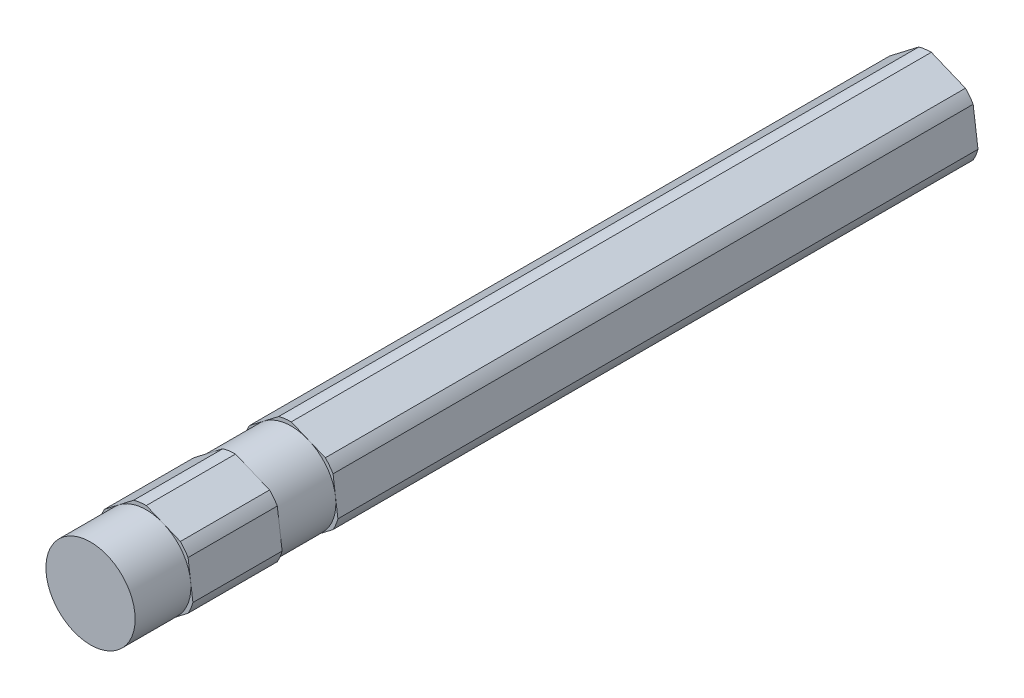
SolidWorks part; units mm, degrees
material "6061-T6 (SS)"
ref_plane "Front Plane" through (0, 0, 0) normal (0, 0, 1) x (1, 0, 0)
ref_plane "Top Plane" through (0, 0, 0) normal (0, 1, 0) x (1, 0, 0)
ref_plane "Right Plane" through (0, 0, 0) normal (1, 0, 0) x (0, 0, -1)
sketch "Sketch1" plane through (0, 0, 0) normal (0, 0, 1) x (1, 0, 0)
  line L1 (-1.7899, 6.6335) -> (-5.9502, 3.4354)
  line L2 (-6.6397, 1.7666) -> (-5.9502, -3.4353)
  line L3 (-4.8498, -4.8668) -> (0, -6.8707)
  line L4 (1.7899, -6.6335) -> (5.9502, -3.4354)
  line L5 (6.6397, -1.7666) -> (5.9502, 3.4353)
  line L6 (4.8498, 4.8668) -> (0, 6.8707)
  circle A0 centre (0, 0) radius 6.35 construction
  arc A1 (-5.9502, 3.4354) -> (-6.6397, 1.7666) centre (0, 0) ccw
  arc A2 (-5.9502, -3.4353) -> (-4.8498, -4.8668) centre (0, 0) ccw
  arc A3 (0, -6.8707) -> (1.7899, -6.6335) centre (0, 0) ccw
  arc A4 (5.9502, -3.4354) -> (6.6397, -1.7666) centre (0, 0) ccw
  arc A5 (5.9502, 3.4353) -> (4.8498, 4.8668) centre (0, 0) ccw
  arc A6 (0, 6.8707) -> (-1.7899, 6.6335) centre (0, 0) ccw
  dimension "D1" = 12.7
  dimension "D2" = 13.7414
extrude "Boss-Extrude1" add sketch "Sketch1" along normal blind 119.6975 contours L1 A1 L2 A2 L3 A3 L4 A4 L5 A5 L6 A6
sketch "Sketch8" plane through (0, 0, 0) normal (0, 0, -1) x (-1, 0, 0)
  point P0 (0, 0)
hole_wizard "1/4-20 Tapped Hole2" positions "Sketch11" profile "Sketch12" tap size "1/4-20" standard "ANSI Inch"
sketch "Sketch11" plane through (0, 0, 0) normal (0, 0, -1) x (-1, 0, 0)
  point P0 (0, 0)
cosmetic thread "Hole Thread5" parameters "D1"=12.7, "D2"=6.35
sketch "Sketch12" plane through (0, 0, 0) normal (1, 0, 0) x (0, 1, 0)
  line L0 (0, 0) -> (0, 18.0438)
  line L1 (0, 18.0438) -> (2.5527, 16.51)
  line L2 (2.5527, 16.51) -> (2.5527, 0)
  line L5 (2.5527, 0) -> (0, 0)
  line L10 (0, 18.0438) -> (-2.5527, 16.51) construction
  line L11 (0, -6.35) -> (0, 107.95) construction
  dimension "Tap Drill Dia." = 5.1054
  dimension "Tap Drill Depth" = 16.51
  dimension "Drill Angle" = 118
sketch "Sketch14" plane through (0, 0, 119.6975) normal (0, 0, 1) x (1, 0, 0)
  line L0 (4.8498, 4.8668) -> (0, 6.8707) construction
  line L7 (-1.7899, 6.6335) -> (-5.9502, 3.4354)
  line L8 (-6.6397, 1.7666) -> (-5.9502, -3.4353)
  line L9 (-4.8498, -4.8668) -> (0, -6.8707)
  line L10 (1.7899, -6.6335) -> (5.9502, -3.4354)
  line L11 (6.6397, -1.7666) -> (5.9502, 3.4353)
  line L12 (4.8498, 4.8668) -> (0, 6.8707)
  line L13 (-1.7899, 6.6335) -> (-5.9502, 3.4354)
  line L14 (-6.6397, 1.7666) -> (-5.9502, -3.4353)
  line L15 (-4.8498, -4.8668) -> (0, -6.8707)
  line L16 (1.7899, -6.6335) -> (5.9502, -3.4354)
  line L17 (6.6397, -1.7666) -> (5.9502, 3.4353)
  line L18 (4.8498, 4.8668) -> (0, 6.8707)
  circle A0 centre (0, 0) radius 6.35
  arc A7 (0, 6.8707) -> (-1.7899, 6.6335) centre (0, 0) ccw
  arc A8 (-5.9502, 3.4354) -> (-6.6397, 1.7666) centre (0, 0) ccw
  arc A9 (-5.9502, -3.4353) -> (-4.8498, -4.8668) centre (0, 0) ccw
  arc A10 (0, -6.8707) -> (1.7899, -6.6335) centre (0, 0) ccw
  arc A11 (5.9502, -3.4354) -> (6.6397, -1.7666) centre (0, 0) ccw
  arc A12 (5.9502, 3.4353) -> (4.8498, 4.8668) centre (0, 0) ccw
  arc A13 (0, 6.8707) -> (-1.7899, 6.6335) centre (0, 0) ccw
  arc A14 (-5.9502, 3.4354) -> (-6.6397, 1.7666) centre (0, 0) ccw
  arc A15 (-5.9502, -3.4353) -> (-4.8498, -4.8668) centre (0, 0) ccw
  arc A16 (0, -6.8707) -> (1.7899, -6.6335) centre (0, 0) ccw
  arc A17 (5.9502, -3.4354) -> (6.6397, -1.7666) centre (0, 0) ccw
  arc A18 (5.9502, 3.4353) -> (4.8498, 4.8668) centre (0, 0) ccw
  arc M2 (0, 6.8707) -> (-1.7899, 6.6335) centre (0, 0) ccw
  line M3 (-1.7899, 6.6335) -> (-5.9502, 3.4354)
  arc M4 (-5.9502, 3.4354) -> (-6.6397, 1.7666) centre (0, 0) ccw
  line M5 (-6.6397, 1.7666) -> (-5.9502, -3.4353)
  arc M6 (-5.9502, -3.4353) -> (-4.8498, -4.8668) centre (0, 0) ccw
  line M7 (-4.8498, -4.8668) -> (0, -6.8707)
  arc M8 (0, -6.8707) -> (1.7899, -6.6335) centre (0, 0) ccw
  line M9 (1.7899, -6.6335) -> (5.9502, -3.4354)
  arc M10 (5.9502, -3.4354) -> (6.6397, -1.7666) centre (0, 0) ccw
  line M11 (6.6397, -1.7666) -> (5.9502, 3.4353)
  arc M12 (5.9502, 3.4353) -> (4.8498, 4.8668) centre (0, 0) ccw
  line M13 (4.8498, 4.8668) -> (0, 6.8707)
  dimension "D1" = 0
extrude "Cut-Extrude1" cut sketch "Sketch14" against normal blind 7.9375 contours A0 L18 M2 M3 | A0 L17 M12 M13 | A0 L16 M10 M11 | A0 L15 M8 M9 | A0 L14 M6 M7 | A0 L13 M4 M5 region at (-0.8491, 6.4059, 119.6975) region at (-5.9722, 2.4677, 119.6975) region at (5.1232, 3.9383, 119.6975) region at (-5.1232, -3.9383, 119.6975) region at (5.9722, -2.4677, 119.6975) region at (0.8491, -6.4059, 119.6975)
ref_plane "Plane1" through (0, 0, 99.06) normal (0, 0, 1) x (1, 0, 0)
sketch "Sketch16" plane through (0, 0, 99.06) normal (0, 0, 1) x (1, 0, 0)
  line L6 (4.8498, 4.8668) -> (0, 6.8707)
  line L7 (6.6397, -1.7666) -> (5.9502, 3.4353)
  line L8 (1.7899, -6.6335) -> (5.9502, -3.4354)
  line L9 (-4.8498, -4.8668) -> (0, -6.8707)
  line L10 (-6.6397, 1.7666) -> (-5.9502, -3.4353)
  line L11 (-1.7899, 6.6335) -> (-5.9502, 3.4354)
  line L12 (4.8498, 4.8668) -> (0, 6.8707)
  line L13 (6.6397, -1.7666) -> (5.9502, 3.4353)
  line L14 (1.7899, -6.6335) -> (5.9502, -3.4354)
  line L15 (-4.8498, -4.8668) -> (0, -6.8707)
  line L16 (-6.6397, 1.7666) -> (-5.9502, -3.4353)
  line L17 (-1.7899, 6.6335) -> (-5.9502, 3.4354)
  arc A1 (0, 6.8707) -> (-1.7899, 6.6335) centre (0, 0) ccw construction
  arc A2 (0, 6.8707) -> (-1.7899, 6.6335) centre (0, 0) ccw
  circle A3 centre (0, 0) radius 6.35
  arc A6 (0, 6.8707) -> (-1.7899, 6.6335) centre (0, 0) ccw
  arc A7 (5.9502, 3.4353) -> (4.8498, 4.8668) centre (0, 0) ccw
  arc A8 (5.9502, -3.4354) -> (6.6397, -1.7666) centre (0, 0) ccw
  arc A9 (0, -6.8707) -> (1.7899, -6.6335) centre (0, 0) ccw
  arc A10 (-5.9502, -3.4353) -> (-4.8498, -4.8668) centre (0, 0) ccw
  arc A11 (-5.9502, 3.4354) -> (-6.6397, 1.7666) centre (0, 0) ccw
  arc A13 (5.9502, 3.4353) -> (4.8498, 4.8668) centre (0, 0) ccw
  arc A14 (5.9502, -3.4354) -> (6.6397, -1.7666) centre (0, 0) ccw
  arc A15 (0, -6.8707) -> (1.7899, -6.6335) centre (0, 0) ccw
  arc A16 (-5.9502, -3.4353) -> (-4.8498, -4.8668) centre (0, 0) ccw
  arc A17 (-5.9502, 3.4354) -> (-6.6397, 1.7666) centre (0, 0) ccw
  dimension "D1" = 0
extrude "Cut-Extrude3" cut sketch "Sketch16" against normal blind 7.9375 contours A3 L12 A2 L17 | L13 A13 L12 A3 | L17 A17 L16 A3 | L14 A14 L13 A3 | L16 A16 L15 A3 | L15 A15 L14 A3 region at (5.1232, 3.9383, 99.06) region at (-0.8491, 6.4059, 99.06) region at (5.9722, -2.4677, 99.06) region at (-5.9722, 2.4677, 99.06) region at (-5.1232, -3.9383, 99.06) region at (0.8491, -6.4059, 99.06)
